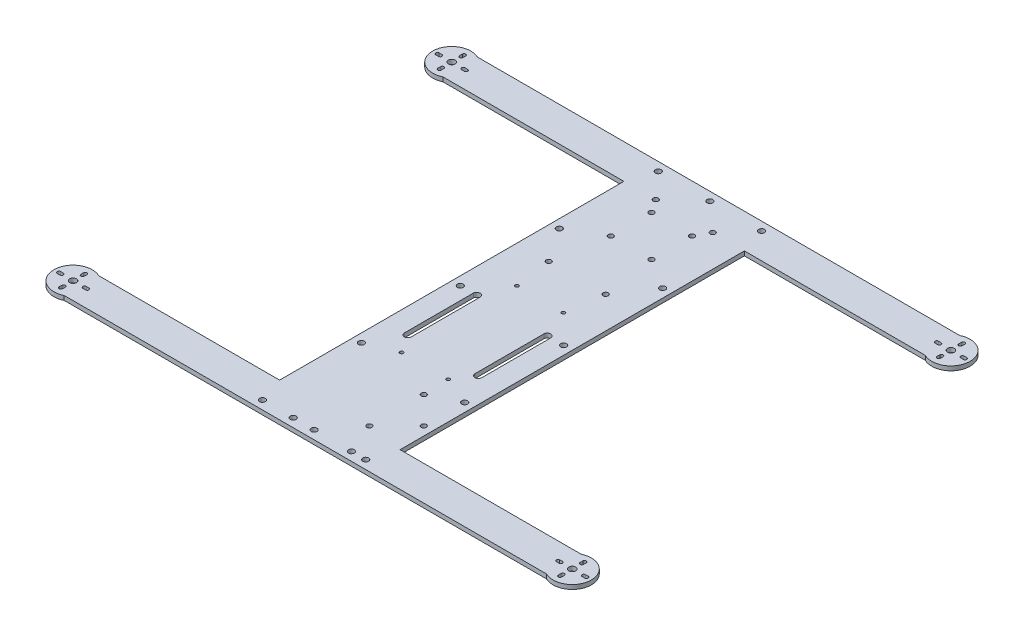
SolidWorks part; units mm, degrees
ref_plane "Front Plane" through (0, 0, 0) normal (0, 0, 1) x (1, 0, 0)
ref_plane "Top Plane" through (0, 0, 0) normal (0, 1, 0) x (1, 0, 0)
ref_plane "Right Plane" through (0, 0, 0) normal (1, 0, 0) x (0, 0, -1)
sketch "Sketch2" plane through (0, 0, 0) normal (0, 1, 0) x (1, 0, 0)
  line L0 (-44.45, 0) -> (44.45, 0) construction
  line L1 (-41.275, 152.4) -> (41.275, 152.4)
  line L2 (-44.45, 149.225) -> (-44.45, -149.225)
  line L3 (-41.275, -152.4) -> (41.275, -152.4)
  line L4 (44.45, 149.225) -> (44.45, -149.225)
  line L5 (0, 152.4) -> (0, -152.4) construction
  arc A0 (-44.45, -149.225) -> (-41.275, -152.4) centre (-41.275, -149.225) ccw
  arc A1 (41.275, -152.4) -> (44.45, -149.225) centre (41.275, -149.225) ccw
  arc A2 (41.275, 152.4) -> (44.45, 149.225) centre (41.275, 149.225) cw
  arc A3 (-41.275, 152.4) -> (-44.45, 149.225) centre (-41.275, 149.225) ccw
  point P8 (0, 0)
  point P13 (-44.45, -152.4)
  point P16 (44.45, -152.4)
  point P21 (-44.45, 152.4)
  dimension "D3" = 3.175
  dimension "D1" = 304.8
  dimension "D2" = 88.9
extrude "Plate Thickness" add sketch "Sketch2" along normal blind 3.175 contours L2 A0 L3 A1 L4 A2 L1 A3
sketch "Sketch10" plane through (0, 3.175, 0) normal (0, 1, 0) x (1, 0, 0)
  line L1 (41.275, 152.4) -> (177.986, 152.4)
  line L2 (41.275, 152.4) -> (41.275, 127)
  line L3 (41.275, 127) -> (177.986, 127)
  line L5 (44.45, 149.225) -> (44.45, -149.225) construction
  line L6 (0, 0) -> (0, 234.1968) construction
  line L7 (0, 0) -> (254.2756, 0) construction
  line L8 (41.275, -127) -> (177.986, -127)
  line L9 (41.275, -152.4) -> (41.275, -127)
  line L10 (41.275, -152.4) -> (177.986, -152.4)
  line L11 (41.275, 152.4) -> (177.986, 152.4)
  line L12 (41.275, 152.4) -> (41.275, 127)
  line L13 (41.275, 127) -> (177.986, 127)
  line L14 (41.275, -127) -> (177.986, -127)
  line L15 (41.275, -152.4) -> (41.275, -127)
  line L16 (41.275, -152.4) -> (177.986, -152.4)
  line L17 (41.275, 152.4) -> (177.986, 152.4)
  line L18 (41.275, 152.4) -> (41.275, 127)
  line L19 (41.275, 127) -> (177.986, 127)
  line L20 (41.275, -127) -> (177.986, -127)
  line L21 (41.275, -152.4) -> (41.275, -127)
  line L22 (41.275, -152.4) -> (177.986, -152.4)
  line L23 (41.275, 152.4) -> (177.986, 152.4)
  line L24 (41.275, 152.4) -> (41.275, 127)
  line L25 (41.275, 127) -> (177.986, 127)
  line L26 (41.275, -127) -> (177.986, -127)
  line L27 (41.275, -152.4) -> (41.275, -127)
  line L28 (41.275, -152.4) -> (177.986, -152.4)
  line L29 (-41.275, -127) -> (-177.986, -127)
  line L30 (-41.275, -152.4) -> (-41.275, -127)
  line L31 (-41.275, -152.4) -> (-177.986, -152.4)
  line L32 (-41.275, 127) -> (-177.986, 127)
  line L33 (-41.275, 152.4) -> (-41.275, 127)
  line L34 (-41.275, 152.4) -> (-177.986, 152.4)
  arc A0 (177.986, 127) -> (177.986, 152.4) centre (184.15, 139.7) ccw
  arc A1 (177.986, -127) -> (177.986, -152.4) centre (184.15, -139.7) cw
  arc A2 (177.986, 127) -> (177.986, 152.4) centre (184.15, 139.7) ccw
  arc A3 (177.986, -127) -> (177.986, -152.4) centre (184.15, -139.7) cw
  arc A4 (177.986, 127) -> (177.986, 152.4) centre (184.15, 139.7) ccw
  arc A5 (177.986, -127) -> (177.986, -152.4) centre (184.15, -139.7) cw
  arc A6 (177.986, 127) -> (177.986, 152.4) centre (184.15, 139.7) ccw
  arc A7 (177.986, -127) -> (177.986, -152.4) centre (184.15, -139.7) cw
  arc A8 (-177.986, -127) -> (-177.986, -152.4) centre (-184.15, -139.7) ccw
  arc A9 (-177.986, 127) -> (-177.986, 152.4) centre (-184.15, 139.7) cw
  arc M45 (-41.275, 152.4) -> (-44.45, 149.225) centre (-41.275, 149.225) ccw
  line M46 (-44.45, 149.225) -> (-44.45, -149.225)
  arc M47 (-44.45, -149.225) -> (-41.275, -152.4) centre (-41.275, -149.225) ccw
  arc M49 (41.275, -152.4) -> (44.45, -149.225) centre (41.275, -149.225) ccw
  line M50 (44.45, -149.225) -> (44.45, 149.225)
  arc M51 (44.45, 149.225) -> (41.275, 152.4) centre (41.275, 149.225) ccw
  dimension "D1" = 139.7
  dimension "D2" = 25.4
extrude "Boss-Extrude1" add sketch "Sketch10" against normal up to surface (3.175 mm away) contours A9 L32 L34 M46 M45 | L3 A0 L1 M51 M50 | A1 L8 L10 M50 M49 | L29 A8 L31 M47 M46 region at (120.5918, 3.175, 139.7067) region at (120.5918, 3.175, -139.7067) region at (-120.5918, 3.175, -139.7067) region at (-120.5918, 3.175, 139.7067) up to face at (0, 0, 0)
sketch "Sketch3" plane through (0, 3.175, 0) normal (0, 1, 0) x (1, 0, 0)
  line L0 (-44.45, 127) -> (-44.45, -127) construction
  line L1 (-177.986, 152.4) -> (177.986, 152.4) construction
  line L2 (-44.45, 0) -> (152.1758, 0) construction
  line L3 (-44.45, 127) -> (-44.45, -127) construction
  line L4 (0, 152.4) -> (0, -152.4) construction
  line L5 (-177.986, -152.4) -> (177.986, -152.4) construction
  circle A0 centre (-38.1, 146.05) radius 2.159
  circle A1 centre (-38.1, 73.025) radius 2.159
  circle A2 centre (-38.1, -73.025) radius 2.159
  circle A3 centre (-38.1, -146.05) radius 2.159
  circle A4 centre (38.1, -146.05) radius 2.159
  circle A5 centre (38.1, -73.025) radius 2.159
  circle A6 centre (38.1, 73.025) radius 2.159
  circle A7 centre (38.1, 146.05) radius 2.159
  circle A8 centre (0, 146.05) radius 2.159
  circle A9 centre (0, -146.05) radius 2.159
  circle A10 centre (-38.1, 0) radius 2.159
  circle A11 centre (38.1, 0) radius 2.159
  dimension "D1" = 4.318
  dimension "D4" = 4.318
  dimension "D2" = 6.35
  dimension "D3" = 6.35
  dimension "D5" = 73.025
  dimension "D6" = 6.35
  dimension "D7" = 73.025
  dimension "D8" = 73.025
  dimension "D9" = 73.025
extrude "Mounting holes" cut sketch "Sketch3" against normal through all
sketch "Sketch4" plane through (0, 3.175, 0) normal (0, 1, 0) x (1, 0, 0)
  line L0 (-21.0058, 48.0812) -> (21.0058, 48.0812) construction
  line L1 (0, 0) -> (0, 139.7) construction
  circle A0 centre (-21.0058, 127.0752) radius 1.905
  circle A1 centre (-21.0058, 48.0812) radius 1.905
  circle A2 centre (21.0058, 48.0812) radius 1.905
  circle A3 centre (21.0058, 127.0752) radius 1.905
  point P13 (0, 48.0812)
  point P17 (0, 69.85)
  point P18 (0, 69.85)
  dimension "D1" = 3.81
  dimension "D2" = 78.994
  dimension "D3" = 42.0116
extrude "Jetson Holes (w/o mount)" cut sketch "Sketch4" against normal through all
sketch "Sketch5" plane through (0, 3.175, 0) normal (0, 1, 0) x (1, 0, 0)
  circle A1 centre (-14.3419, 117.2351) radius 1.905
  circle A3 centre (15.6555, 117.2351) radius 1.905
  circle A4 centre (15.6555, 87.2377) radius 1.905
  circle A5 centre (-14.3419, 87.2377) radius 1.905
  dimension "D1" = 3.81
  dimension "D2" = 29.9974
  dimension "D3" = 29.9974
extrude "PDB holes" cut sketch "Sketch5" against normal through all
sketch "Sketch6" plane through (0, 3.175, 0) normal (0, 1, 0) x (1, 0, 0)
  circle A6 centre (38.0032, -103.0828) radius 1.905
  circle A7 centre (17.9372, -83.0168) radius 1.905
  circle A8 centre (17.9372, -123.1488) radius 1.905
  dimension "D5" = 3.81
  dimension "D6" = 40.132
  dimension "D7" = 20.066
  dimension "D8" = 20.066
extrude "Lidar Holes" cut sketch "Sketch6" against normal through all
sketch "Sketch7" plane through (0, 3.175, 0) normal (0, 1, 0) x (1, 0, 0)
  line L0 (0, 152.4) -> (0, -152.4) construction
  line L1 (-177.986, 152.4) -> (177.986, 152.4) construction
  line L2 (-177.986, -152.4) -> (177.986, -152.4) construction
  line L3 (17.145, 20.7699) -> (-17.145, 20.7699) construction
  circle A0 centre (-17.145, 20.7699) radius 1.27
  circle A1 centre (-17.145, -64.3201) radius 1.27
  circle A2 centre (17.145, -64.3201) radius 1.27
  circle A3 centre (17.145, 20.7699) radius 1.27
  point P14 (0, 20.7699)
  dimension "D1" = 2.54
  dimension "D2" = 85.09
  dimension "D3" = 34.29
extrude "PixHawk Holes" cut sketch "Sketch7" against normal through all
sketch "Sketch8" plane through (0, 3.175, 0) normal (0, 1, 0) x (1, 0, 0)
  line L0 (0, 152.4) -> (0, -115.5095) construction
  line L1 (-177.986, 152.4) -> (177.986, 152.4) construction
  line L2 (-26.035, -0.006) -> (-26.035, -50.806) construction
  line L3 (-23.495, -0.006) -> (-23.495, -50.806)
  line L4 (-28.575, -0.006) -> (-28.575, -50.806)
  line L5 (26.035, -0.006) -> (26.035, -50.806) construction
  line L6 (23.495, -0.006) -> (23.495, -50.806)
  line L7 (28.575, -0.006) -> (28.575, -50.806)
  arc A0 (-23.495, -0.006) -> (-28.575, -0.006) centre (-26.035, -0.006) ccw
  arc A1 (-28.575, -50.806) -> (-23.495, -50.806) centre (-26.035, -50.806) ccw
  arc A2 (23.495, -0.006) -> (28.575, -0.006) centre (26.035, -0.006) cw
  arc A3 (28.575, -50.806) -> (23.495, -50.806) centre (26.035, -50.806) cw
  point P7 (-26.035, -25.406)
  point P14 (26.035, -25.406)
  dimension "D1" = 50.8
  dimension "D2" = 5.08
  dimension "D3" = 26.035
extrude "Battery Holes" cut sketch "Sketch8" against normal through all
sketch "Sketch9" plane through (0, 3.175, 0) normal (0, 1, 0) x (1, 0, 0)
  line L0 (-177.986, -152.4) -> (177.986, -152.4) construction
  line L1 (-177.986, 152.4) -> (177.986, 152.4) construction
  line L2 (-43.782, -152.4) -> (43.782, -152.4) construction
  line L3 (-43.782, -152.4) -> (-43.782, -139.298) construction
  line L4 (-43.782, -139.298) -> (43.782, -139.298) construction
  line L5 (43.782, -152.4) -> (43.782, -139.298) construction
  circle A0 centre (-15.4076, -146.05) radius 2.159
  circle A1 centre (27.592, -146.05) radius 2.159
  point P10 (0, -139.298)
  point P13 (0, 152.4)
  dimension "D1" = 4.318
  dimension "D2" = 4.318
  dimension "D3" = 42.9997
  dimension "D4" = 6.35
  dimension "D5" = 87.564
  dimension "D6" = 16.19
extrude "Stereo Cam" cut sketch "Sketch9" against normal through all contours A0 | A1
sketch "Sketch11" plane through (0, 3.175, 0) normal (0, 1, 0) x (1, 0, 0)
  line L0 (173.65, 139.7) -> (175.65, 139.7) construction
  line L1 (173.65, 140.95) -> (175.65, 140.95)
  line L2 (173.65, 138.45) -> (175.65, 138.45)
  line L3 (184.15, 139.7) -> (184.15, 143.0164) construction
  line L4 (194.65, 139.7) -> (192.65, 139.7) construction
  line L5 (194.65, 140.95) -> (192.65, 140.95)
  line L6 (194.65, 138.45) -> (192.65, 138.45)
  line L7 (184.15, 148.7) -> (184.15, 146.7) construction
  line L8 (185.4, 148.7) -> (185.4, 146.7)
  line L9 (182.9, 148.7) -> (182.9, 146.7)
  line L10 (184.15, 139.7) -> (199.8184, 139.7) construction
  line L11 (184.15, 130.7) -> (184.15, 132.7) construction
  line L12 (185.4, 130.7) -> (185.4, 132.7)
  line L13 (182.9, 130.7) -> (182.9, 132.7)
  line L14 (44.45, 127) -> (44.45, -127) construction
  line L15 (-177.986, 152.4) -> (177.986, 152.4) construction
  line L16 (0, 0) -> (0, 273.2731) construction
  line L19 (0, 0) -> (202.4297, 0) construction
  line L22 (184.15, -139.7) -> (199.8184, -139.7) construction
  line L25 (184.15, -139.7) -> (184.15, -143.0164) construction
  line L28 (184.15, -130.7) -> (184.15, -132.7) construction
  line L29 (185.4, -130.7) -> (185.4, -132.7)
  line L30 (182.9, -130.7) -> (182.9, -132.7)
  line L33 (184.15, -148.7) -> (184.15, -146.7) construction
  line L36 (185.4, -148.7) -> (185.4, -146.7)
  line L39 (182.9, -148.7) -> (182.9, -146.7)
  line L42 (194.65, -139.7) -> (192.65, -139.7) construction
  line L43 (194.65, -140.95) -> (192.65, -140.95)
  line L44 (194.65, -138.45) -> (192.65, -138.45)
  line L45 (173.65, -139.7) -> (175.65, -139.7) construction
  line L46 (173.65, -140.95) -> (175.65, -140.95)
  line L49 (173.65, -138.45) -> (175.65, -138.45)
  line L52 (-184.15, -139.7) -> (-184.15, -143.0164) construction
  line L55 (-184.15, -139.7) -> (-199.8184, -139.7) construction
  line L58 (-173.65, -139.7) -> (-175.65, -139.7) construction
  line L59 (-173.65, -140.95) -> (-175.65, -140.95)
  line L60 (-173.65, -138.45) -> (-175.65, -138.45)
  line L61 (-184.15, -148.7) -> (-184.15, -146.7) construction
  line L62 (-185.4, -148.7) -> (-185.4, -146.7)
  line L63 (-182.9, -148.7) -> (-182.9, -146.7)
  line L64 (-184.15, -130.7) -> (-184.15, -132.7) construction
  line L65 (-185.4, -130.7) -> (-185.4, -132.7)
  line L66 (-182.9, -130.7) -> (-182.9, -132.7)
  line L67 (-194.65, -139.7) -> (-192.65, -139.7) construction
  line L68 (-194.65, -140.95) -> (-192.65, -140.95)
  line L69 (-194.65, -138.45) -> (-192.65, -138.45)
  line L70 (-184.15, 139.7) -> (-199.8184, 139.7) construction
  line L71 (-184.15, 139.7) -> (-184.15, 143.0164) construction
  line L72 (-184.15, 130.7) -> (-184.15, 132.7) construction
  line L73 (-185.4, 130.7) -> (-185.4, 132.7)
  line L74 (-182.9, 130.7) -> (-182.9, 132.7)
  line L75 (-184.15, 148.7) -> (-184.15, 146.7) construction
  line L76 (-185.4, 148.7) -> (-185.4, 146.7)
  line L77 (-182.9, 148.7) -> (-182.9, 146.7)
  line L78 (-194.65, 139.7) -> (-192.65, 139.7) construction
  line L79 (-194.65, 140.95) -> (-192.65, 140.95)
  line L80 (-194.65, 138.45) -> (-192.65, 138.45)
  line L81 (-173.65, 139.7) -> (-175.65, 139.7) construction
  line L82 (-173.65, 140.95) -> (-175.65, 140.95)
  line L83 (-173.65, 138.45) -> (-175.65, 138.45)
  circle A0 centre (184.15, 139.7) radius 2.5
  arc A1 (173.65, 140.95) -> (173.65, 138.45) centre (173.65, 139.7) ccw
  arc A2 (175.65, 138.45) -> (175.65, 140.95) centre (175.65, 139.7) ccw
  arc A4 (194.65, 140.95) -> (194.65, 138.45) centre (194.65, 139.7) cw
  arc A5 (192.65, 138.45) -> (192.65, 140.95) centre (192.65, 139.7) cw
  arc A6 (185.4, 148.7) -> (182.9, 148.7) centre (184.15, 148.7) ccw
  arc A7 (182.9, 146.7) -> (185.4, 146.7) centre (184.15, 146.7) ccw
  arc A8 (185.4, 130.7) -> (182.9, 130.7) centre (184.15, 130.7) cw
  arc A9 (182.9, 132.7) -> (185.4, 132.7) centre (184.15, 132.7) cw
  circle A37 centre (184.15, -139.7) radius 2.5
  arc A38 (185.4, -130.7) -> (182.9, -130.7) centre (184.15, -130.7) ccw
  arc A39 (182.9, -132.7) -> (185.4, -132.7) centre (184.15, -132.7) ccw
  arc A40 (185.4, -148.7) -> (182.9, -148.7) centre (184.15, -148.7) cw
  arc A41 (182.9, -146.7) -> (185.4, -146.7) centre (184.15, -146.7) cw
  arc A42 (194.65, -140.95) -> (194.65, -138.45) centre (194.65, -139.7) ccw
  arc A43 (192.65, -138.45) -> (192.65, -140.95) centre (192.65, -139.7) ccw
  arc A44 (173.65, -140.95) -> (173.65, -138.45) centre (173.65, -139.7) cw
  arc A45 (175.65, -138.45) -> (175.65, -140.95) centre (175.65, -139.7) cw
  circle A46 centre (-184.15, -139.7) radius 2.5
  arc A47 (-173.65, -140.95) -> (-173.65, -138.45) centre (-173.65, -139.7) ccw
  arc A48 (-175.65, -138.45) -> (-175.65, -140.95) centre (-175.65, -139.7) ccw
  arc A49 (-185.4, -148.7) -> (-182.9, -148.7) centre (-184.15, -148.7) ccw
  arc A50 (-182.9, -146.7) -> (-185.4, -146.7) centre (-184.15, -146.7) ccw
  arc A51 (-185.4, -130.7) -> (-182.9, -130.7) centre (-184.15, -130.7) cw
  arc A52 (-182.9, -132.7) -> (-185.4, -132.7) centre (-184.15, -132.7) cw
  arc A53 (-194.65, -140.95) -> (-194.65, -138.45) centre (-194.65, -139.7) cw
  arc A54 (-192.65, -138.45) -> (-192.65, -140.95) centre (-192.65, -139.7) cw
  circle A55 centre (-184.15, 139.7) radius 2.5
  arc A56 (-185.4, 130.7) -> (-182.9, 130.7) centre (-184.15, 130.7) ccw
  arc A57 (-182.9, 132.7) -> (-185.4, 132.7) centre (-184.15, 132.7) ccw
  arc A58 (-185.4, 148.7) -> (-182.9, 148.7) centre (-184.15, 148.7) cw
  arc A59 (-182.9, 146.7) -> (-185.4, 146.7) centre (-184.15, 146.7) cw
  arc A60 (-194.65, 140.95) -> (-194.65, 138.45) centre (-194.65, 139.7) ccw
  arc A61 (-192.65, 138.45) -> (-192.65, 140.95) centre (-192.65, 139.7) ccw
  arc A62 (-173.65, 140.95) -> (-173.65, 138.45) centre (-173.65, 139.7) cw
  arc A63 (-175.65, 138.45) -> (-175.65, 140.95) centre (-175.65, 139.7) cw
  point P5 (174.65, 139.7)
  point P16 (193.65, 139.7)
  point P23 (184.15, 147.7)
  point P31 (184.15, 131.7)
  point P47 (184.15, -131.7)
  point P54 (184.15, -147.7)
  point P61 (193.65, -139.7)
  point P68 (174.65, -139.7)
  point P79 (-174.65, -139.7)
  point P86 (-184.15, -147.7)
  point P93 (-184.15, -131.7)
  point P100 (-193.65, -139.7)
  point P111 (-184.15, 131.7)
  point P118 (-184.15, 147.7)
  point P125 (-193.65, 139.7)
  point P132 (-174.65, 139.7)
  dimension "D1" = 5
  dimension "D2" = 2.5
  dimension "D3" = 2
  dimension "D4" = 19
  dimension "D5" = 2.5
  dimension "D6" = 2
  dimension "D7" = 16
  dimension "D8" = 139.7
  dimension "D9" = 12.7
extrude "motor mounting" cut sketch "Sketch11" against normal through all
